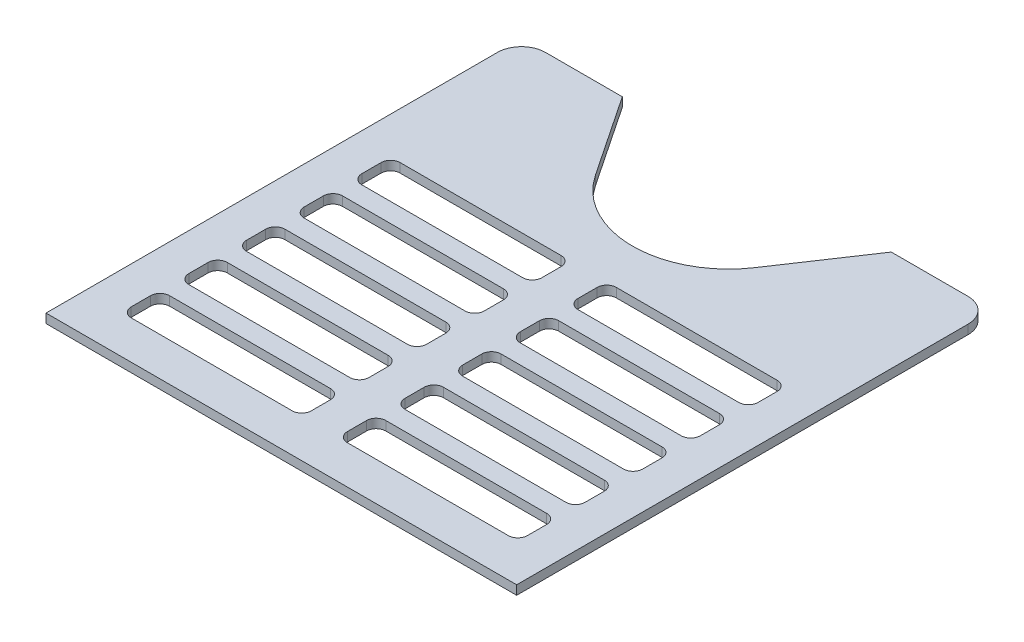
SolidWorks part; units mm, degrees
material "PVC hart"
ref_plane "Ebene vorne" through (0, 0, 0) normal (0, 0, 1) x (1, 0, 0)
ref_plane "Ebene oben" through (0, 0, 0) normal (0, 1, 0) x (1, 0, 0)
ref_plane "Ebene rechts" through (0, 0, 0) normal (1, 0, 0) x (0, 0, -1)
sketch "Skizze2" plane through (0, 0, 0) normal (0, 1, 0) x (1, 0, 0)
  line L0 (0, 82.3632) -> (0, -81.2206) construction
  line L6 (-44, 50) -> (-28, 50)
  line L7 (-28, 50) -> (-16.6199, 33)
  line L8 (28, 50) -> (16.6199, 33)
  line L9 (44, 50) -> (28, 50)
  line L10 (-49, -49) -> (-49, 45)
  line L11 (49, -49) -> (49, 45)
  line L12 (-49, -49) -> (49, -49)
  arc A0 (-16.6199, 33) -> (16.6199, 33) centre (0, 44.1257) ccw
  arc A1 (49, 45) -> (44, 50) centre (44, 45) ccw
  arc A2 (-49, 45) -> (-44, 50) centre (-44, 45) cw
  point P0 (0, 0)
  point P3 (49, 50)
  point P16 (-49, 50)
  dimension "D1" = 20
  dimension "D8" = 5
  dimension "D2" = 49
  dimension "D3" = 99
  dimension "D4" = 21
  dimension "D5" = 17
  dimension "D6" = 49
  dimension "D7" = 49
extrude "Aufsatz-Linear austragen2" add sketch "Skizze2" along normal blind 1.9
sketch "Skizze3" plane through (0, 1.9, 0) normal (0, 1, 0) x (1, 0, 0)
  line L0 (0, 51.615) -> (0, -55.1924) construction
  line L1 (-28, 50) -> (-44, 50) construction
  line L2 (-39.25, 15) -> (-5.75, 15)
  line L3 (-41.25, 13) -> (-41.25, 9)
  line L4 (-39.25, 7) -> (-5.75, 7)
  line L5 (-3.75, 13) -> (-3.75, 9)
  line L6 (-41.25, 15) -> (-3.75, 7) construction
  line L7 (-41.25, 7) -> (-3.75, 15) construction
  line L36 (3.75, 13) -> (3.75, 9)
  line L37 (5.75, 15) -> (39.25, 15)
  line L38 (41.25, 13) -> (41.25, 9)
  line L39 (5.75, 7) -> (39.25, 7)
  line L40 (3.75, 1) -> (3.75, -3)
  line L41 (5.75, 3) -> (39.25, 3)
  line L42 (41.25, 1) -> (41.25, -3)
  line L43 (5.75, -5) -> (39.25, -5)
  line L44 (3.75, -11) -> (3.75, -15)
  line L45 (5.75, -9) -> (39.25, -9)
  line L46 (41.25, -11) -> (41.25, -15)
  line L47 (5.75, -17) -> (39.25, -17)
  line L48 (3.75, -23) -> (3.75, -27)
  line L49 (5.75, -21) -> (39.25, -21)
  line L50 (41.25, -23) -> (41.25, -27)
  line L51 (5.75, -29) -> (39.25, -29)
  line L52 (3.75, -35) -> (3.75, -39)
  line L53 (5.75, -33) -> (39.25, -33)
  line L54 (41.25, -35) -> (41.25, -39)
  line L55 (5.75, -41) -> (39.25, -41)
  line L56 (-41.25, 1) -> (-41.25, -3)
  line L57 (-39.25, 3) -> (-5.75, 3)
  line L58 (-3.75, 1) -> (-3.75, -3)
  line L59 (-39.25, -5) -> (-5.75, -5)
  line L60 (-41.25, -11) -> (-41.25, -15)
  line L61 (-39.25, -9) -> (-5.75, -9)
  line L62 (-3.75, -11) -> (-3.75, -15)
  line L63 (-39.25, -17) -> (-5.75, -17)
  line L64 (-41.25, -23) -> (-41.25, -27)
  line L65 (-39.25, -21) -> (-5.75, -21)
  line L66 (-3.75, -23) -> (-3.75, -27)
  line L67 (-39.25, -29) -> (-5.75, -29)
  line L68 (-41.25, -35) -> (-41.25, -39)
  line L69 (-39.25, -33) -> (-5.75, -33)
  line L70 (-3.75, -35) -> (-3.75, -39)
  line L71 (-39.25, -41) -> (-5.75, -41)
  arc A0 (41.25, 9) -> (39.25, 7) centre (39.25, 9) cw
  arc A1 (39.25, 15) -> (41.25, 13) centre (39.25, 13) cw
  arc A2 (3.75, 13) -> (5.75, 15) centre (5.75, 13) cw
  arc A3 (3.75, 9) -> (5.75, 7) centre (5.75, 9) ccw
  arc A4 (3.75, -3) -> (5.75, -5) centre (5.75, -3) ccw
  arc A5 (3.75, 1) -> (5.75, 3) centre (5.75, 1) cw
  arc A6 (39.25, 3) -> (41.25, 1) centre (39.25, 1) cw
  arc A7 (41.25, -3) -> (39.25, -5) centre (39.25, -3) cw
  arc A8 (39.25, -9) -> (41.25, -11) centre (39.25, -11) cw
  arc A9 (41.25, -15) -> (39.25, -17) centre (39.25, -15) cw
  arc A10 (3.75, -15) -> (5.75, -17) centre (5.75, -15) ccw
  arc A11 (3.75, -11) -> (5.75, -9) centre (5.75, -11) cw
  arc A12 (3.75, -27) -> (5.75, -29) centre (5.75, -27) ccw
  arc A13 (3.75, -23) -> (5.75, -21) centre (5.75, -23) cw
  arc A14 (39.25, -21) -> (41.25, -23) centre (39.25, -23) cw
  arc A15 (41.25, -27) -> (39.25, -29) centre (39.25, -27) cw
  arc A16 (41.25, -39) -> (39.25, -41) centre (39.25, -39) cw
  arc A17 (39.25, -33) -> (41.25, -35) centre (39.25, -35) cw
  arc A18 (3.75, -39) -> (5.75, -41) centre (5.75, -39) ccw
  arc A19 (3.75, -35) -> (5.75, -33) centre (5.75, -35) cw
  arc A20 (-5.75, -33) -> (-3.75, -35) centre (-5.75, -35) cw
  arc A21 (-3.75, -39) -> (-5.75, -41) centre (-5.75, -39) cw
  arc A22 (-41.25, -39) -> (-39.25, -41) centre (-39.25, -39) ccw
  arc A23 (-41.25, -35) -> (-39.25, -33) centre (-39.25, -35) cw
  arc A24 (-5.75, -21) -> (-3.75, -23) centre (-5.75, -23) cw
  arc A25 (-3.75, -27) -> (-5.75, -29) centre (-5.75, -27) cw
  arc A26 (-41.25, -27) -> (-39.25, -29) centre (-39.25, -27) ccw
  arc A27 (-41.25, -23) -> (-39.25, -21) centre (-39.25, -23) cw
  arc A28 (-3.75, -15) -> (-5.75, -17) centre (-5.75, -15) cw
  arc A29 (-5.75, -9) -> (-3.75, -11) centre (-5.75, -11) cw
  arc A30 (-41.25, -15) -> (-39.25, -17) centre (-39.25, -15) ccw
  arc A31 (-41.25, -11) -> (-39.25, -9) centre (-39.25, -11) cw
  arc A32 (-3.75, -3) -> (-5.75, -5) centre (-5.75, -3) cw
  arc A33 (-5.75, 3) -> (-3.75, 1) centre (-5.75, 1) cw
  arc A34 (-41.25, -3) -> (-39.25, -5) centre (-39.25, -3) ccw
  arc A35 (-41.25, 1) -> (-39.25, 3) centre (-39.25, 1) cw
  arc A36 (-5.75, 7) -> (-3.75, 9) centre (-5.75, 9) ccw
  arc A37 (-41.25, 9) -> (-39.25, 7) centre (-39.25, 9) ccw
  arc A38 (-39.25, 15) -> (-41.25, 13) centre (-39.25, 13) ccw
  arc A39 (-5.75, 15) -> (-3.75, 13) centre (-5.75, 13) cw
  point P3 (-22.5, 11)
  dimension "D7" = 2
  dimension "D1" = 37.5
  dimension "D2" = 8
  dimension "D3" = 22.5
  dimension "D4" = 35
  dimension "D5" = 2
  dimension "D6" = 5
extrude "Schnitt-Linear austragen2" cut sketch "Skizze3" against normal up to surface (1.9 mm away) up to face at (0, 0, -25.1197)
